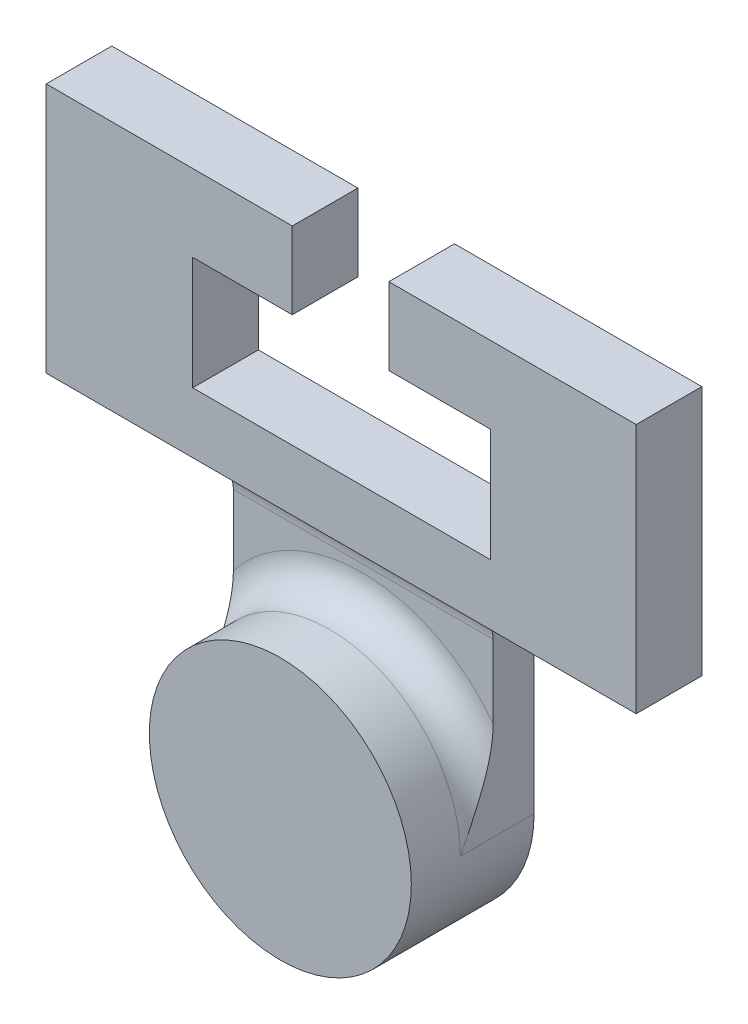
SolidWorks part; units mm, degrees
material "6061 Alloy"
ref_plane "Front Plane" through (0, 0, 0) normal (0, 0, 1) x (1, 0, 0)
ref_plane "Top Plane" through (0, 0, 0) normal (0, 1, 0) x (1, 0, 0)
ref_plane "Right Plane" through (0, 0, 0) normal (1, 0, 0) x (0, 0, -1)
sketch "Sketch1" plane through (0, 0, 0) normal (0, 0, 1) x (1, 0, 0)
  circle A0 centre (0, 0) radius 10.16
  dimension "D1" = 20.32
extrude "Boss-Extrude1" add sketch "Sketch1" against normal blind 9.525
sketch "Sketch2" plane through (0, 0, -9.525) normal (0, 0, -1) x (-1, 0, 0)
  line L1 (-10.16, 0) -> (9.9915, 0)
  line L2 (-10.16, 0) -> (-10.16, 15.7545)
  line L3 (-10.16, 15.7545) -> (9.9915, 15.7545)
  line L4 (9.9915, 0) -> (9.9915, 15.7545)
  circle A0 centre (0, 0) radius 10.16 construction
extrude "Boss-Extrude4" add sketch "Sketch2" against normal blind 3.175
sketch "Sketch3" plane through (0, 15.7545, 0) normal (0, 1, 0) x (1, 0, 0)
  line L0 (-9.9915, 9.525) -> (-22.594, 9.525)
  line L1 (-22.594, 9.525) -> (-22.594, 4.4351)
  line L2 (-22.594, 4.4351) -> (23.1661, 4.4351)
  line L3 (23.1661, 4.4351) -> (23.1661, 9.525)
  line L4 (23.1661, 9.525) -> (-9.9915, 9.525)
extrude "Boss-Extrude5" add sketch "Sketch3" along normal blind 4.699
sketch "Sketch4" plane through (0, 20.4535, 0) normal (0, 1, 0) x (1, 0, 0)
  line L0 (-22.594, 4.4351) -> (23.1661, 4.4351) construction
  line L1 (-22.594, 9.525) -> (-11.2293, 9.525)
  line L2 (-22.594, 9.525) -> (-22.594, 4.4351)
  line L3 (-22.594, 4.4351) -> (-11.2293, 4.4351)
  line L4 (-11.2293, 9.525) -> (-11.2293, 4.4351)
  line L5 (23.1661, 9.525) -> (-22.594, 9.525) construction
  line L6 (23.1661, 9.525) -> (11.852, 9.525)
  line L7 (23.1661, 9.525) -> (23.1661, 4.4351)
  line L8 (23.1661, 4.4351) -> (11.852, 4.4351)
  line L9 (11.852, 9.525) -> (11.852, 4.4351)
extrude "Boss-Extrude6" add sketch "Sketch4" along normal blind 8.763
sketch "Sketch5" plane through (0, 29.2165, 0) normal (0, 1, 0) x (1, 0, 0)
  line L0 (-11.2293, 4.4351) -> (11.852, 4.4351) construction
  line L1 (-22.594, 9.525) -> (-3.5102, 9.525)
  line L2 (-22.594, 9.525) -> (-22.594, 4.4351)
  line L3 (-22.594, 4.4351) -> (-3.5102, 4.4351)
  line L4 (-3.5102, 9.525) -> (-3.5102, 4.4351)
  line L6 (23.1661, 9.525) -> (3.9811, 9.525)
  line L7 (23.1661, 9.525) -> (23.1661, 4.4351)
  line L8 (23.1661, 4.4351) -> (3.9811, 4.4351)
  line L9 (3.9811, 9.525) -> (3.9811, 4.4351)
extrude "Boss-Extrude7" add sketch "Sketch5" along normal blind 5.969
fillet "Fillet1" radius 2.54 1 edges at (0.9251, 10.1178, -6.35)
fillet "Fillet2" radius 2.54 1 edges at (0.0842, 15.7545, -6.35)
